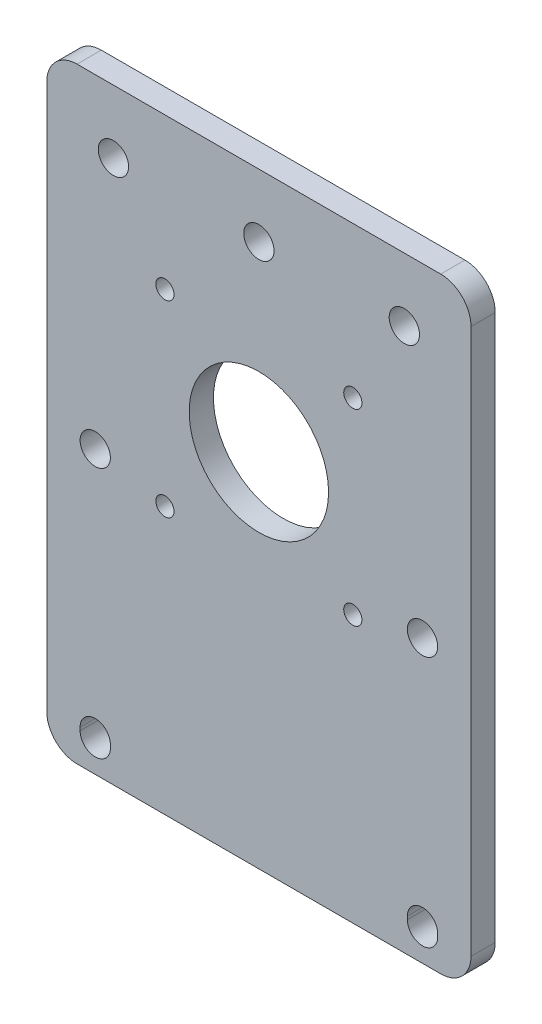
SolidWorks part; units mm, degrees
ref_plane "Front" through (0, 0, 0) normal (0, 0, 1) x (1, 0, 0)
ref_plane "Top" through (0, 0, 0) normal (0, 1, 0) x (1, 0, 0)
ref_plane "Right" through (0, 0, 0) normal (1, 0, 0) x (0, 0, -1)
sketch "Sketch4" plane through (0, 0, 0) normal (0, 0, 1) x (1, 0, 0)
  line L0 (-27, -44.5) -> (-27, -45) construction
  line L1 (-35, 50) -> (35, 50)
  line L2 (-35, 50) -> (-35, -50)
  line L3 (-35, -50) -> (35, -50)
  line L4 (35, 50) -> (35, -50)
  line L5 (-35, 50) -> (35, -50) construction
  line L6 (-35, -50) -> (35, 50) construction
  line L7 (-24.5, -44.5) -> (-24.5, -45)
  line L8 (-29.5, -44.5) -> (-29.5, -45)
  line L9 (0, -47.1607) -> (0, 39.6245) construction
  line L10 (27, -44.5) -> (27, -45) construction
  line L11 (24.5, -44.5) -> (24.5, -45)
  line L12 (29.5, -44.5) -> (29.5, -45)
  circle A0 centre (-27, -3.5) radius 2.5
  arc A1 (-24.5, -44.5) -> (-29.5, -44.5) centre (-27, -44.5) ccw
  arc A2 (-29.5, -45) -> (-24.5, -45) centre (-27, -45) ccw
  arc A3 (24.5, -44.5) -> (29.5, -44.5) centre (27, -44.5) cw
  arc A4 (29.5, -45) -> (24.5, -45) centre (27, -45) cw
  circle A5 centre (27, -3.5) radius 2.5
  point P0 (0, 0)
  point P10 (-27, -44.75)
  point P19 (27, -44.75)
  dimension "D3" = 27
  dimension "D6" = 2.5
  dimension "D8" = 5
  dimension "D1" = 70
  dimension "D2" = 100
  dimension "D4" = 41
  dimension "D5" = 0.5
  dimension "D7" = 5
extrude "Boss-Extrude2" add sketch "Sketch4" along normal blind 4
sketch "Sketch5" plane through (0, 0, 4) normal (0, 0, 1) x (1, 0, 0)
  line L0 (0, 46.583) -> (0, -17.262) construction
  line L1 (-44.8343, 9.5767) -> (52.8956, 9.5767) construction
  circle A0 centre (0, 9.5767) radius 11.5
  circle A1 centre (27, -3.5) radius 2.5 construction
  circle A2 centre (-15.5, 25.0767) radius 1.5
  circle A9 centre (15.5, 25.0767) radius 1.5
  circle A10 centre (15.5, -5.9233) radius 1.5
  circle A11 centre (-15.5, -5.9233) radius 1.5
  dimension "D1" = 23
  dimension "D3" = 3
  dimension "D2" = 30
  dimension "D4" = 15.5
  dimension "D5" = 15.5
extrude "Cut-Extrude2" cut sketch "Sketch5" against normal through all
sketch "Sketch6" plane through (0, 0, 4) normal (0, 0, 1) x (1, 0, 0)
  line L0 (0, 37.2831) -> (0, 4.0651) construction
  line L1 (-10, 49.5767) -> (10, 49.5767) construction
  line L2 (-10, 49.5767) -> (-10, 29.5767) construction
  line L3 (-10, 29.5767) -> (10, 29.5767) construction
  line L4 (10, 49.5767) -> (10, 29.5767) construction
  line L5 (-10, 49.5767) -> (10, 29.5767) construction
  line L6 (-10, 29.5767) -> (10, 49.5767) construction
  circle A0 centre (0, 9.5767) radius 11.5 construction
  circle A1 centre (24, 39.5767) radius 2.5
  circle A2 centre (-24, 39.5767) radius 2.5
  circle A3 centre (0, 39.5767) radius 2.5
  point P0 (0, 39.5767)
  dimension "D4" = 5
  dimension "D6" = 5
  dimension "D1" = 20
  dimension "D2" = 20
  dimension "D3" = 30
  dimension "D5" = 24
extrude "Cut-Extrude3" cut sketch "Sketch6" against normal through all
fillet "Fillet1" radius 5 4 edges at (-35, -50, 2) (35, -50, 2) (35, 50, 2) (-35, 50, 2)
